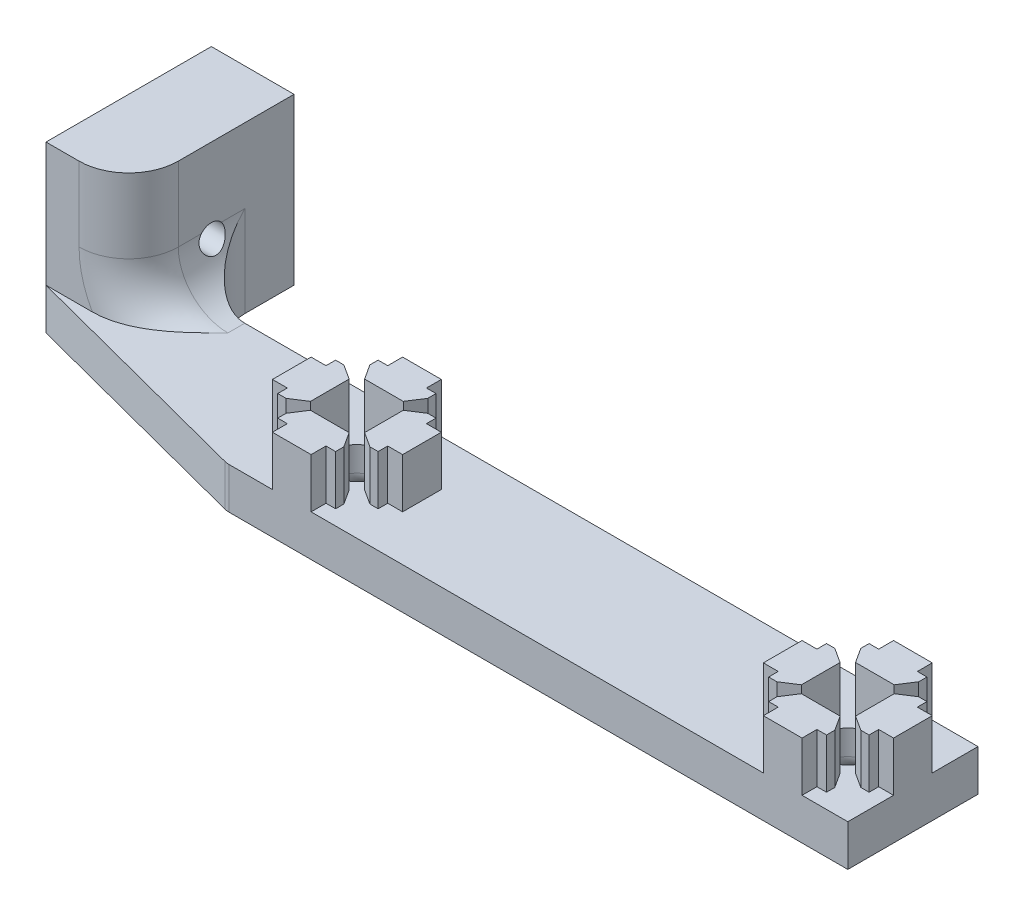
SolidWorks part; units mm, degrees
ref_plane "Front Plane" through (0, 0, 0) normal (0, 0, 1) x (1, 0, 0)
ref_plane "Top Plane" through (0, 0, 0) normal (0, 1, 0) x (1, 0, 0)
ref_plane "Right Plane" through (0, 0, 0) normal (1, 0, 0) x (0, 0, -1)
sketch "Sketch1" plane through (0, 0, 0) normal (0, 1, 0) x (1, 0, 0)
  line L0 (-2.9718, 10) -> (-2.9718, 7.714)
  line L1 (-10, 10) -> (10, 10)
  line L2 (-10, 10) -> (-10, -10)
  line L3 (-10, -10) -> (10, -10)
  line L4 (10, 10) -> (10, -10)
  line L5 (-10, 10) -> (10, -10) construction
  line L6 (-10, -10) -> (10, 10) construction
  line L7 (-2.9718, 10) -> (2.9718, 10) construction
  line L8 (-2.9718, 10) -> (-2.9718, 4.158) construction
  line L9 (-2.9718, 4.158) -> (2.9718, 4.158) construction
  line L10 (2.9718, 10) -> (2.9718, 4.158) construction
  line L11 (-4.445, 7.714) -> (4.445, 7.714) construction
  line L12 (-4.445, 7.714) -> (-4.445, 6.444) construction
  line L13 (-4.445, 6.444) -> (4.445, 6.444) construction
  line L14 (4.445, 7.714) -> (4.445, 6.444) construction
  line L15 (-4.445, 7.714) -> (4.445, 6.444) construction
  line L16 (-4.445, 6.444) -> (4.445, 7.714) construction
  line L17 (-2.9718, 7.714) -> (-4.445, 7.714)
  line L18 (-4.445, 7.714) -> (-4.445, 6.444)
  line L19 (-4.445, 6.444) -> (-2.9718, 4.158)
  line L20 (-2.9718, 4.158) -> (2.9718, 4.158)
  line L21 (2.9718, 4.158) -> (4.445, 6.444)
  line L22 (4.445, 6.444) -> (4.445, 7.714)
  line L23 (4.445, 7.714) -> (2.9718, 7.714)
  line L24 (2.9718, 7.714) -> (2.9718, 10)
  line L25 (2.9718, 10) -> (-2.9718, 10)
  line L26 (4.158, -2.9718) -> (4.158, 2.9718)
  line L27 (4.158, 2.9718) -> (6.444, 4.445)
  line L28 (6.444, 4.445) -> (7.714, 4.445)
  line L29 (7.714, 4.445) -> (7.714, 2.9718)
  line L30 (7.714, 2.9718) -> (10, 2.9718)
  line L31 (10, -2.9718) -> (10, 2.9718) construction
  line L32 (10, 2.9718) -> (10, -2.9718)
  line L33 (10, -2.9718) -> (7.714, -2.9718)
  line L34 (7.714, -2.9718) -> (7.714, -4.445)
  line L35 (7.714, -4.445) -> (6.444, -4.445)
  line L36 (6.444, -4.445) -> (4.158, -2.9718)
  line L37 (2.9718, -10) -> (-2.9718, -10) construction
  line L38 (4.445, -6.444) -> (2.9718, -4.158)
  line L39 (4.445, -7.714) -> (4.445, -6.444)
  line L40 (2.9718, -7.714) -> (4.445, -7.714)
  line L41 (2.9718, -10) -> (2.9718, -7.714)
  line L42 (-2.9718, -10) -> (2.9718, -10)
  line L43 (-2.9718, -7.714) -> (-2.9718, -10)
  line L44 (-4.445, -7.714) -> (-2.9718, -7.714)
  line L45 (-4.445, -6.444) -> (-4.445, -7.714)
  line L46 (-2.9718, -4.158) -> (-4.445, -6.444)
  line L47 (2.9718, -4.158) -> (-2.9718, -4.158)
  line L48 (-10, 2.9718) -> (-10, -2.9718) construction
  line L49 (-10, -2.9718) -> (-10, 2.9718)
  line L50 (-7.714, -2.9718) -> (-10, -2.9718)
  line L51 (-7.714, -4.445) -> (-7.714, -2.9718)
  line L52 (-6.444, -4.445) -> (-7.714, -4.445)
  line L53 (-4.158, -2.9718) -> (-6.444, -4.445)
  line L54 (-4.158, 2.9718) -> (-4.158, -2.9718)
  line L55 (-6.444, 4.445) -> (-4.158, 2.9718)
  line L56 (-7.714, 4.445) -> (-6.444, 4.445)
  line L57 (-7.714, 2.9718) -> (-7.714, 4.445)
  line L58 (-10, 2.9718) -> (-7.714, 2.9718)
  line L59 (0, 7.079) -> (0, 7.714) construction
  point P0 (0, 0)
  point P12 (0, 4.158)
  point P13 (0, 7.079)
  dimension "D3" = 10
  dimension "D1" = 20
  dimension "D2" = 20
  dimension "D4" = 5.9436
  dimension "D5" = 10
  dimension "D6" = 5.842
  dimension "D7" = 2.286
  dimension "D8" = 3.556
  dimension "D9" = 8.89
extrude "Boss-Extrude1" add sketch "Sketch1" along normal blind 7.62 contours L23 L24 L1 L0 L17 L18 L19 L20 L21 L22 | L26 L27 L28 L29 L30 L32 L33 L34 L35 L36 | L49 L58 L57 L56 L55 L54 L53 L52 L51 L50 | L38 L47 L46 L45 L44 L43 L42 L41 L40 L39 region at (0, 0, -6.9665)
sketch "Sketch2" plane through (0, 0, 0) normal (0, -1, 0) x (1, 0, 0)
  line L1 (10, -10) -> (-122.9538, -10)
  line L2 (10, -10) -> (10, 10)
  line L3 (10, 10) -> (-122.9538, 10)
  line L4 (-122.9538, -10) -> (-122.9538, 10)
  line L5 (10, -10) -> (-122.9538, 10) construction
  line L6 (10, 10) -> (-122.9538, -10) construction
  line L7 (-2.9718, -10) -> (2.9718, -10) construction
  line L8 (10, -2.9718) -> (10, 2.9718) construction
  dimension "D1" = 132.9538
  dimension "D2" = 20
  dimension "D3" = 0
  dimension "D4" = 0
extrude "Boss-Extrude2" add sketch "Sketch2" along normal blind 6.35
pattern_linear "LPattern2" count 2 spacing 75.4126 along (-1, 0, 0) of "Boss-Extrude1"
sketch "Sketch4" plane through (0, -6.35, 0) normal (0, -1, 0) x (-1, 0, 0)
  line L0 (122.9538, 10) -> (122.9538, -0.2108) construction
  line L1 (122.9538, -10) -> (122.9538, 10) construction
  line L2 (122.9538, -10) -> (85.4126, -10)
  line L3 (-10, -10) -> (122.9538, -10) construction
  line L4 (85.4126, -10) -> (122.9538, -0.2108)
  line L5 (122.9538, -0.2108) -> (122.9538, -10)
  dimension "D1" = 10.2108
  dimension "D2" = 37.5412
extrude "Cut-Extrude1" cut sketch "Sketch4" against normal through all
fillet "Fillet1" radius 2.54 1 edges at (-85.4126, -3.175, 10)
sketch "Sketch6" plane through (-122.9538, 0, 0) normal (-1, 0, 0) x (0, 0, 1)
  line L1 (0.2108, -6.35) -> (-25.1892, -6.35)
  line L2 (0.2108, -6.35) -> (0.2108, 19.05)
  line L3 (0.2108, 19.05) -> (-25.1892, 19.05)
  line L4 (-25.1892, -6.35) -> (-25.1892, 19.05)
  dimension "D1" = 25.4
  dimension "D2" = 25.4
extrude "Boss-Extrude7" add sketch "Sketch6" against normal blind 12.7
fillet "Fillet3" radius 7.62 2 edges at (-110.2538, 0, -4.8946) (-110.2538, -3.175, -10)
fillet "Fillet5" radius 7.62 2 edges at (-108.022, 2.2318, 0.2108) (-110.2538, 13.335, 0.2108)
sketch "Sketch11" plane through (-122.9538, 0, 0) normal (-1, 0, 0) x (0, 0, 1)
  line L0 (-25.1892, -6.35) -> (0.2108, 19.05) construction
  circle A0 centre (-12.4892, 6.35) radius 1.9844
  dimension "D1" = 3.9688
extrude "Cut-Extrude3" cut sketch "Sketch11" against normal through all
sketch "Sketch13" plane through (0, 0, 0) normal (0, 1, 0) x (1, 0, 0)
  line L0 (-79.5706, -2.9718) -> (-81.8566, -4.445) construction
  line L1 (4.158, 2.9718) -> (-4.158, 2.9718) construction
  line L2 (4.158, 2.9718) -> (4.158, -2.9718) construction
  line L3 (4.158, -2.9718) -> (-4.158, -2.9718) construction
  line L4 (-4.158, 2.9718) -> (-4.158, -2.9718) construction
  line L5 (-71.2546, 2.9718) -> (-79.5706, 2.9718) construction
  line L6 (-71.2546, 2.9718) -> (-71.2546, -2.9718) construction
  line L7 (-71.2546, -2.9718) -> (-79.5706, -2.9718) construction
  line L8 (-79.5706, 2.9718) -> (-79.5706, -2.9718) construction
  line L9 (-79.5706, 2.9718) -> (-79.5706, -2.9718) construction
  line L10 (-75.4126, 2.9718) -> (-75.4126, -2.9718) construction
  circle A0 centre (0, 0) radius 3.5
  circle A1 centre (-75.4126, 0) radius 3.5
  dimension "D1" = 7
  dimension "D2" = 7
extrude "Cut-Extrude5" cut sketch "Sketch13" against normal through all
fillet "Fillet6" radius 2.54 2 edges at (0, -6.35, 3.5) (-75.4126, -6.35, 3.5)
